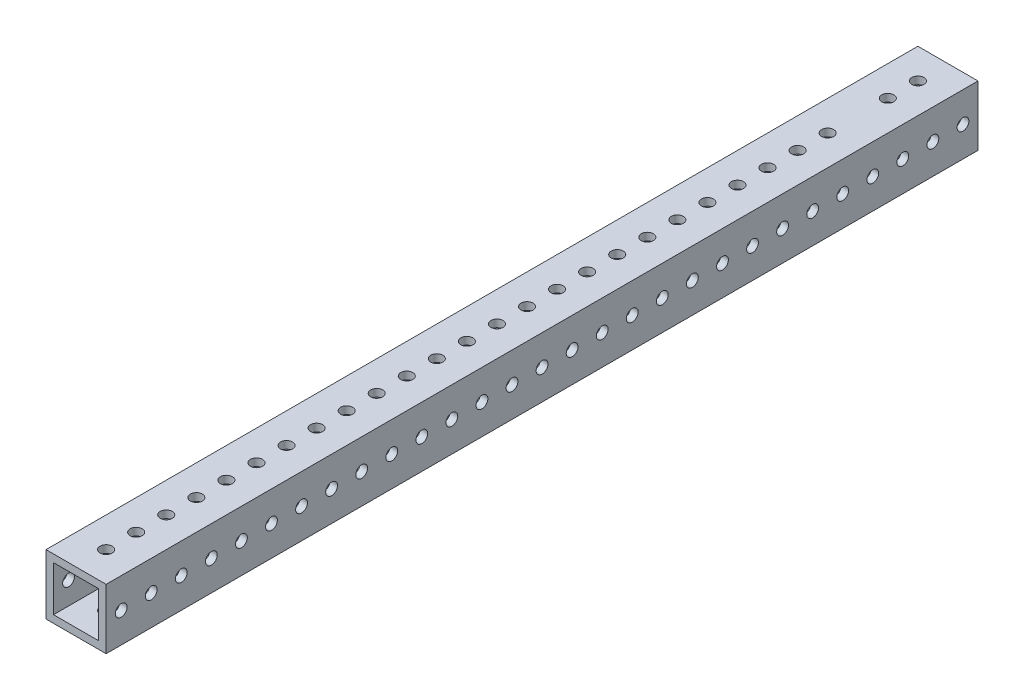
SolidWorks part; units mm, degrees
material "6061-T6 (SS)"
ref_plane "Front Plane" through (0, 0, 0) normal (0, 0, 1) x (1, 0, 0)
ref_plane "Top Plane" through (0, 0, 0) normal (0, 1, 0) x (1, 0, 0)
ref_plane "Right Plane" through (0, 0, 0) normal (1, 0, 0) x (0, 0, -1)
sketch "Sketch1" plane through (0, 0, 0) normal (0, 0, 1) x (1, 0, 0)
  line L0 (-9.525, 9.525) -> (9.525, 9.525)
  line L1 (-12.7, 12.7) -> (12.7, 12.7)
  line L2 (-12.7, 12.7) -> (-12.7, -12.7)
  line L3 (-12.7, -12.7) -> (12.7, -12.7)
  line L4 (12.7, 12.7) -> (12.7, -12.7)
  line L5 (9.525, 9.525) -> (9.525, -9.525)
  line L6 (-9.525, -9.525) -> (9.525, -9.525)
  line L7 (-9.525, 9.525) -> (-9.525, -9.525)
  line L8 (-12.7, 12.7) -> (12.7, -12.7) construction
  line L9 (12.7, 12.7) -> (-12.7, -12.7) construction
  point P5 (0, 0)
  dimension "D1" = 25.4
  dimension "D2" = 25.4
  dimension "D3" = 3.175
extrude "Boss-Extrude1" add sketch "Sketch1" along normal mid plane 368.3
sketch "Sketch2" plane through (0, 12.7, 0) normal (0, 1, 0) x (1, 0, 0)
  line L0 (12.7, -184.15) -> (-12.7, -184.15) construction
  line L1 (-12.7, -184.15) -> (-12.7, 184.15) construction
  line L4 (12.7, 184.15) -> (-12.7, 184.15) construction
  circle A0 centre (12.7, -171.45) radius 2.5527 construction
  circle A1 centre (25.4, -171.45) radius 2.5527 construction
  circle A2 centre (0, -171.45) radius 2.5527
  circle A3 centre (0, -158.75) radius 2.5527
  circle A4 centre (12.7, -158.75) radius 2.5527 construction
  circle A5 centre (25.4, -158.75) radius 2.5527 construction
  circle A6 centre (0, -146.05) radius 2.5527
  circle A7 centre (12.7, -146.05) radius 2.5527 construction
  circle A8 centre (25.4, -146.05) radius 2.5527 construction
  circle A9 centre (0, -133.35) radius 2.5527
  circle A10 centre (12.7, -133.35) radius 2.5527 construction
  circle A11 centre (25.4, -133.35) radius 2.5527 construction
  circle A12 centre (0, -120.65) radius 2.5527
  circle A13 centre (12.7, -120.65) radius 2.5527 construction
  circle A14 centre (25.4, -120.65) radius 2.5527 construction
  circle A15 centre (0, -107.95) radius 2.5527
  circle A16 centre (12.7, -107.95) radius 2.5527 construction
  circle A17 centre (25.4, -107.95) radius 2.5527 construction
  circle A18 centre (0, -95.25) radius 2.5527
  circle A19 centre (12.7, -95.25) radius 2.5527 construction
  circle A20 centre (25.4, -95.25) radius 2.5527 construction
  circle A21 centre (0, -82.55) radius 2.5527
  circle A22 centre (12.7, -82.55) radius 2.5527 construction
  circle A23 centre (25.4, -82.55) radius 2.5527 construction
  circle A24 centre (0, -69.85) radius 2.5527
  circle A25 centre (12.7, -69.85) radius 2.5527 construction
  circle A26 centre (25.4, -69.85) radius 2.5527 construction
  circle A27 centre (0, -57.15) radius 2.5527
  circle A28 centre (12.7, -57.15) radius 2.5527 construction
  circle A29 centre (25.4, -57.15) radius 2.5527 construction
  circle A30 centre (0, -44.45) radius 2.5527
  circle A31 centre (12.7, -44.45) radius 2.5527 construction
  circle A32 centre (25.4, -44.45) radius 2.5527 construction
  circle A33 centre (0, -31.75) radius 2.5527
  circle A34 centre (12.7, -31.75) radius 2.5527 construction
  circle A35 centre (25.4, -31.75) radius 2.5527 construction
  circle A36 centre (0, -19.05) radius 2.5527
  circle A37 centre (12.7, -19.05) radius 2.5527 construction
  circle A38 centre (25.4, -19.05) radius 2.5527 construction
  circle A39 centre (0, -6.35) radius 2.5527
  circle A40 centre (12.7, -6.35) radius 2.5527 construction
  circle A41 centre (25.4, -6.35) radius 2.5527 construction
  circle A42 centre (0, 6.35) radius 2.5527
  circle A43 centre (12.7, 6.35) radius 2.5527 construction
  circle A44 centre (25.4, 6.35) radius 2.5527 construction
  circle A45 centre (0, 19.05) radius 2.5527
  circle A46 centre (12.7, 19.05) radius 2.5527 construction
  circle A47 centre (25.4, 19.05) radius 2.5527 construction
  circle A48 centre (0, 31.75) radius 2.5527
  circle A49 centre (12.7, 31.75) radius 2.5527 construction
  circle A50 centre (25.4, 31.75) radius 2.5527 construction
  circle A51 centre (0, 44.45) radius 2.5527
  circle A52 centre (12.7, 44.45) radius 2.5527 construction
  circle A53 centre (25.4, 44.45) radius 2.5527 construction
  circle A54 centre (0, 57.15) radius 2.5527
  circle A55 centre (12.7, 57.15) radius 2.5527 construction
  circle A56 centre (25.4, 57.15) radius 2.5527 construction
  circle A57 centre (0, 69.85) radius 2.5527
  circle A58 centre (12.7, 69.85) radius 2.5527 construction
  circle A59 centre (25.4, 69.85) radius 2.5527 construction
  circle A60 centre (0, 82.55) radius 2.5527
  circle A61 centre (12.7, 82.55) radius 2.5527 construction
  circle A62 centre (25.4, 82.55) radius 2.5527 construction
  circle A63 centre (0, 95.25) radius 2.5527
  circle A64 centre (12.7, 95.25) radius 2.5527 construction
  circle A65 centre (25.4, 95.25) radius 2.5527 construction
  circle A66 centre (0, 107.95) radius 2.5527
  circle A67 centre (12.7, 107.95) radius 2.5527 construction
  circle A68 centre (25.4, 107.95) radius 2.5527 construction
  circle A69 centre (0, 120.65) radius 2.5527
  circle A70 centre (12.7, 120.65) radius 2.5527 construction
  circle A71 centre (25.4, 120.65) radius 2.5527 construction
  circle A72 centre (0, 133.35) radius 2.5527
  circle A73 centre (12.7, 133.35) radius 2.5527 construction
  circle A74 centre (25.4, 133.35) radius 2.5527 construction
  circle A75 centre (0, 146.05) radius 2.5527 construction
  circle A76 centre (12.7, 146.05) radius 2.5527 construction
  circle A77 centre (25.4, 146.05) radius 2.5527
  circle A78 centre (0, 158.75) radius 2.5527
  circle A79 centre (12.7, 158.75) radius 2.5527 construction
  circle A80 centre (25.4, 158.75) radius 2.5527 construction
  circle A81 centre (0, 171.45) radius 2.5527
  circle A82 centre (12.7, 171.45) radius 2.5527 construction
  circle A83 centre (25.4, 171.45) radius 2.5527 construction
  circle A84 centre (0, 184.15) radius 2.5527 construction
  circle A85 centre (12.7, 184.15) radius 2.5527 construction
  circle A86 centre (25.4, 184.15) radius 2.5527 construction
  circle A87 centre (0, 196.85) radius 2.5527
  circle A88 centre (12.7, 196.85) radius 2.5527 construction
  circle A89 centre (25.4, 196.85) radius 2.5527 construction
  circle A90 centre (0, 209.55) radius 2.5527
  circle A91 centre (12.7, 209.55) radius 2.5527 construction
  circle A92 centre (25.4, 209.55) radius 2.5527 construction
  circle A93 centre (0, 222.25) radius 2.5527
  circle A94 centre (12.7, 222.25) radius 2.5527 construction
  circle A95 centre (25.4, 222.25) radius 2.5527 construction
  circle A96 centre (0, 234.95) radius 2.5527
  circle A97 centre (12.7, 234.95) radius 2.5527 construction
  circle A98 centre (25.4, 234.95) radius 2.5527 construction
  circle A99 centre (0, 247.65) radius 2.5527
  circle A100 centre (12.7, 247.65) radius 2.5527 construction
  circle A101 centre (25.4, 247.65) radius 2.5527 construction
  circle A108 centre (0, 273.05) radius 2.5527 [skipped]
  circle A109 centre (12.7, 273.05) radius 2.5527 [skipped]
  circle A110 centre (25.4, 273.05) radius 2.5527 [skipped]
  circle A111 centre (0, 260.35) radius 2.5527 [skipped]
  circle A112 centre (12.7, 260.35) radius 2.5527 [skipped]
  circle A113 centre (25.4, 260.35) radius 2.5527 [skipped]
  circle A114 centre (25.4, 260.35) radius 2.5527 construction
  circle A115 centre (12.7, 260.35) radius 2.5527 construction
  circle A116 centre (0, 260.35) radius 2.5527
  circle A117 centre (25.4, 273.05) radius 2.5527 construction
  circle A118 centre (12.7, 273.05) radius 2.5527 construction
  circle A119 centre (0, 273.05) radius 2.5527
  circle A120 centre (25.4, 285.75) radius 2.5527 construction
  circle A121 centre (12.7, 285.75) radius 2.5527 construction
  circle A122 centre (0, 285.75) radius 2.5527
  circle A123 centre (25.4, 298.45) radius 2.5527 construction
  circle A124 centre (12.7, 298.45) radius 2.5527 construction
  circle A125 centre (0, 298.45) radius 2.5527
  circle A126 centre (25.4, 311.15) radius 2.5527 construction
  circle A127 centre (12.7, 311.15) radius 2.5527 construction
  circle A128 centre (0, 311.15) radius 2.5527
  circle A129 centre (25.4, 323.85) radius 2.5527 construction
  circle A130 centre (12.7, 323.85) radius 2.5527 construction
  circle A131 centre (0, 323.85) radius 2.5527
  circle A132 centre (25.4, 336.55) radius 2.5527 construction
  circle A133 centre (12.7, 336.55) radius 2.5527 construction
  circle A134 centre (0, 336.55) radius 2.5527
  circle A135 centre (25.4, 349.25) radius 2.5527 construction
  circle A136 centre (12.7, 349.25) radius 2.5527 construction
  circle A137 centre (0, 349.25) radius 2.5527
  circle A138 centre (25.4, 361.95) radius 2.5527 construction
  circle A139 centre (12.7, 361.95) radius 2.5527 construction
  circle A140 centre (0, 361.95) radius 2.5527
  circle A141 centre (25.4, 374.65) radius 2.5527 construction
  circle A142 centre (12.7, 374.65) radius 2.5527 construction
  circle A143 centre (0, 374.65) radius 2.5527
  circle A144 centre (25.4, 387.35) radius 2.5527 construction
  circle A145 centre (12.7, 387.35) radius 2.5527 construction
  circle A146 centre (0, 387.35) radius 2.5527
  circle A147 centre (25.4, 400.05) radius 2.5527 construction
  circle A148 centre (12.7, 400.05) radius 2.5527 construction
  circle A149 centre (0, 400.05) radius 2.5527
  circle A150 centre (25.4, 412.75) radius 2.5527 construction
  circle A151 centre (12.7, 412.75) radius 2.5527 construction
  circle A152 centre (0, 412.75) radius 2.5527
  dimension "D2" = 5.1054
  dimension "D4" = 12.7
  dimension "D1" = 12.7
  dimension "D3" = 25.4
  dimension "D6" = 12.7
  dimension "D7" = 63.5
  dimension "D5" = 36
  dimension "D8" = 14
extrude "Cut-Extrude1" cut sketch "Sketch2" against normal through all
sketch "Sketch4" plane through (12.7, 0, 0) normal (1, 0, 0) x (0, 0, -1)
  line L1 (-184.15, -12.7) -> (-184.15, 12.7) construction
  line L2 (-184.15, -12.7) -> (184.15, -12.7) construction
  circle A2 centre (-177.8, 0) radius 2.4892
  circle A3 centre (-165.1, 0) radius 2.4892
  circle A16 centre (-152.4, 0) radius 2.4892
  circle A17 centre (-139.7, 0) radius 2.4892
  circle A18 centre (-127, 0) radius 2.4892
  circle A19 centre (254, 0) radius 2.4892
  circle A20 centre (266.7, 0) radius 2.4892
  circle A21 centre (279.4, 0) radius 2.4892
  circle A22 centre (292.1, 0) radius 2.4892
  circle A23 centre (304.8, 0) radius 2.4892
  circle A24 centre (317.5, 0) radius 2.4892
  circle A25 centre (330.2, 0) radius 2.4892
  circle A26 centre (342.9, 0) radius 2.4892
  circle A27 centre (355.6, 0) radius 2.4892
  circle A28 centre (368.3, 0) radius 2.4892
  circle A29 centre (381, 0) radius 2.4892
  circle A30 centre (393.7, 0) radius 2.4892
  circle A31 centre (406.4, 0) radius 2.4892
  circle A32 centre (419.1, 0) radius 2.4892
  circle A35 centre (-114.3, 0) radius 2.4892
  circle A36 centre (-101.6, 0) radius 2.4892
  circle A37 centre (-88.9, 0) radius 2.4892
  circle A38 centre (-76.2, 0) radius 2.4892
  circle A39 centre (-63.5, 0) radius 2.4892
  circle A40 centre (-50.8, 0) radius 2.4892
  circle A41 centre (-38.1, 0) radius 2.4892
  circle A42 centre (-25.4, 0) radius 2.4892
  circle A43 centre (-12.7, 0) radius 2.4892
  circle A44 centre (0, 0) radius 2.4892
  circle A45 centre (12.7, 0) radius 2.4892
  circle A46 centre (25.4, 0) radius 2.4892
  circle A47 centre (38.1, 0) radius 2.4892
  circle A48 centre (50.8, 0) radius 2.4892
  circle A49 centre (63.5, 0) radius 2.4892
  circle A50 centre (76.2, 0) radius 2.4892
  circle A51 centre (88.9, 0) radius 2.4892
  circle A52 centre (101.6, 0) radius 2.4892
  circle A53 centre (114.3, 0) radius 2.4892
  circle A54 centre (127, 0) radius 2.4892
  circle A55 centre (139.7, 0) radius 2.4892
  circle A56 centre (152.4, 0) radius 2.4892
  circle A57 centre (165.1, 0) radius 2.4892
  circle A58 centre (177.8, 0) radius 2.4892
  circle A59 centre (190.5, 0) radius 2.4892
  circle A60 centre (203.2, 0) radius 2.4892
  circle A61 centre (215.9, 0) radius 2.4892
  circle A62 centre (228.6, 0) radius 2.4892
  circle A63 centre (241.3, 0) radius 2.4892
  dimension "D2" = 4.9784
  dimension "D1" = 6.35
  dimension "D3" = 12.7
  dimension "D4" = 12.7
  dimension "D5" = 34
  dimension "D6" = 10
  dimension "D7" = 6
extrude "Cut-Extrude3" cut sketch "Sketch4" against normal through all
